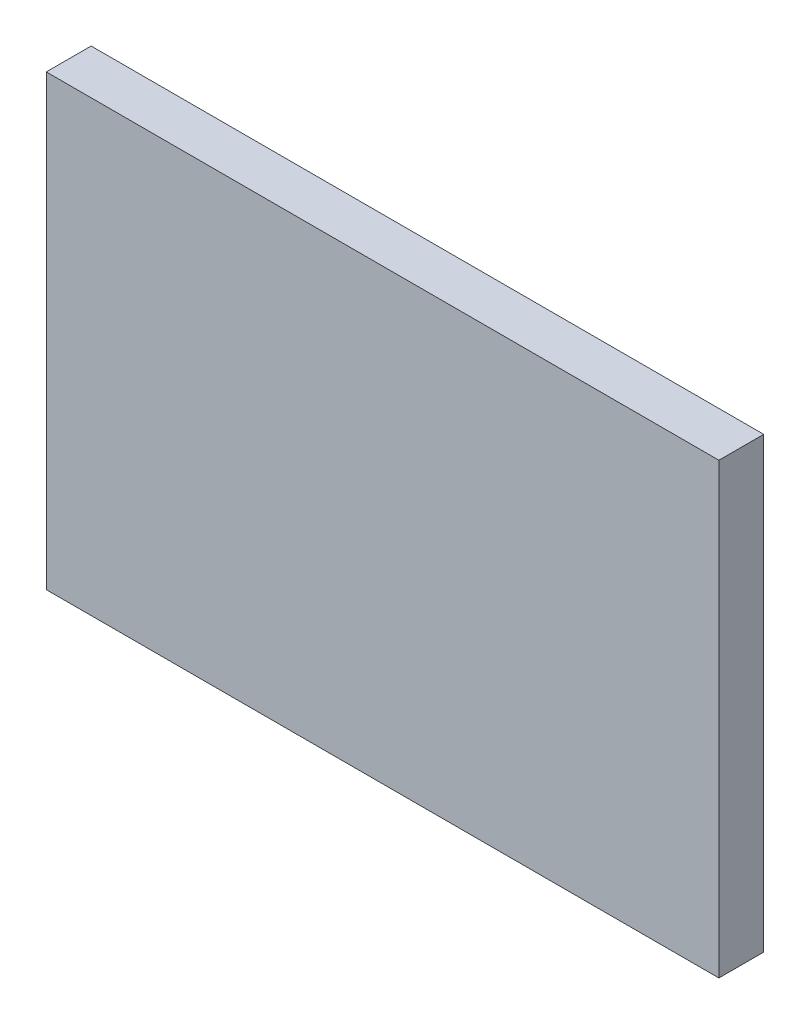
SolidWorks part; units mm, degrees
material "Лист 4,0 ГОСТ 19903-2015 / Ст3сп ГОСТ 14637-89"
ref_plane "Спереди" through (0, 0, 0) normal (0, 0, 1) x (1, 0, 0)
ref_plane "Сверху" through (0, 0, 0) normal (0, 1, 0) x (1, 0, 0)
ref_plane "Справа" through (0, 0, 0) normal (1, 0, 0) x (0, 0, -1)
sketch "Эскиз1" plane through (0, 0, 0) normal (0, 0, 1) x (1, 0, 0)
  line L1 (-30, -20) -> (30, -20)
  line L2 (-30, -20) -> (-30, 20)
  line L3 (-30, 20) -> (30, 20)
  line L4 (30, -20) -> (30, 20)
base flange "Базовая кромка1" sketch "Эскиз1" thickness 4 reverse thickness direction no parameters "D1"=4
sketch "Сгиб-Линии1" [suppressed] plane through (0, 0, 0) normal (0, 1, 0) x (1, 0, 0)
sketch "Граничная рамка1" [suppressed] plane through (0, 0, 0) normal (0, 1, 0) x (1, 0, 0)
sheet metal parameters "Листовой металл30" thickness 4 parameters "D1"=4
flat pattern "Развертка30" [suppressed]
sketch "Сгиб-Линии2" plane through (0, 0, 0) normal (0, 1, 0) x (1, 0, 0)
sketch3d "Граничная рамка2" [suppressed]
  line L0 (30, -20, 0) -> (-30, -20, 0) construction
  line L1 (30, 20, 0) -> (-30, 20, 0) construction
  line L2 (30, -20, 0) -> (30, 20, 0) construction
  line L3 (-30, -20, 0) -> (-30, 20, 0) construction
